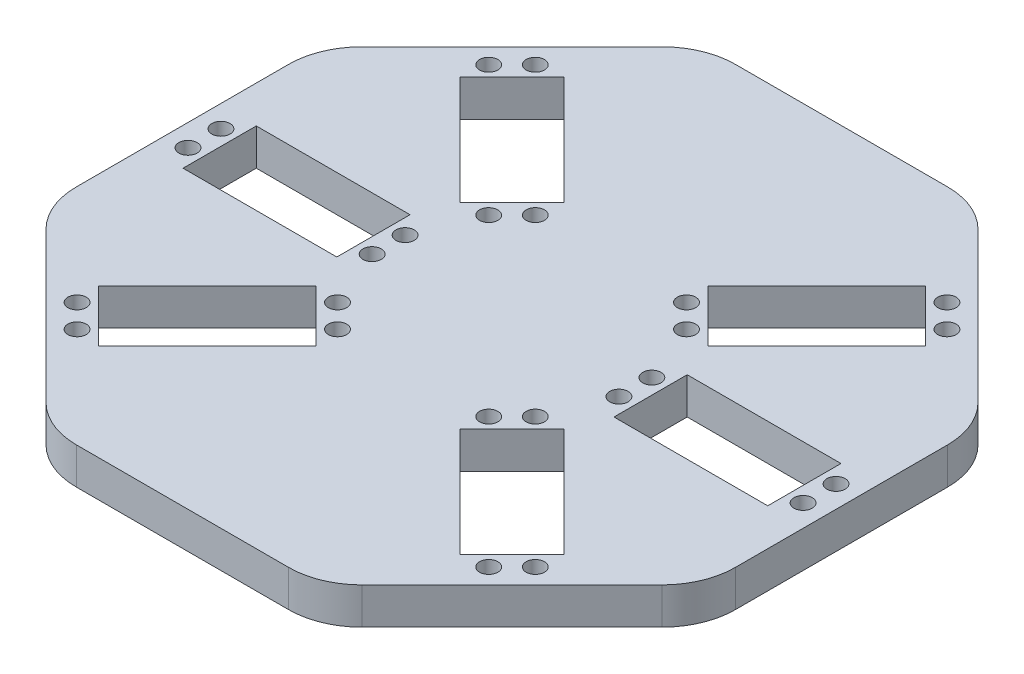
SolidWorks part; units mm, degrees
ref_plane "Front Plane" through (0, 0, 0) normal (0, 0, 1) x (1, 0, 0)
ref_plane "Top Plane" through (0, 0, 0) normal (0, 1, 0) x (1, 0, 0)
ref_plane "Right Plane" through (0, 0, 0) normal (1, 0, 0) x (0, 0, -1)
sketch "Sketch1" plane through (0, 0, 0) normal (0, 1, 0) x (1, 0, 0)
  line L0 (20.6475, -27.0115) -> (56.215, -62.579)
  line L1 (-90, -37.2792) -> (-37.2792, -90)
  line L2 (-37.2792, -90) -> (37.2792, -90)
  line L3 (37.2792, -90) -> (90, -37.2792)
  line L4 (90, -37.2792) -> (90, 37.2792)
  line L5 (90, 37.2792) -> (37.2792, 90)
  line L6 (37.2792, 90) -> (-37.2792, 90)
  line L7 (-37.2792, 90) -> (-90, 37.2792)
  line L8 (-90, 37.2792) -> (-90, -37.2792)
  line L9 (20.6475, -27.0115) -> (27.0115, -20.6475)
  line L10 (56.215, -62.579) -> (62.579, -56.215)
  line L11 (27.0115, -20.6475) -> (62.579, -56.215)
  line L12 (63.6396, -63.6396) -> (0, 0) construction
  line L13 (33.8351, -19.6929) -> (19.6929, -33.8351)
  line L14 (33.8351, -19.6929) -> (63.5335, -49.3914)
  line L15 (19.6929, -33.8351) -> (49.3914, -63.5335)
  line L16 (63.5335, -49.3914) -> (49.3914, -63.5335)
  line L17 (10, -37.85) -> (-10, -37.85) [skipped]
  line L18 (10, -37.85) -> (10, -79.85) [skipped]
  line L19 (10, -79.85) -> (-10, -79.85) [skipped]
  line L20 (-10, -37.85) -> (-10, -79.85) [skipped]
  line L21 (-19.6929, -33.8351) -> (-33.8351, -19.6929)
  line L22 (-19.6929, -33.8351) -> (-49.3914, -63.5335)
  line L23 (-49.3914, -63.5335) -> (-63.5335, -49.3914)
  line L24 (-33.8351, -19.6929) -> (-63.5335, -49.3914)
  line L25 (-37.85, -10) -> (-37.85, 10)
  line L26 (-37.85, -10) -> (-79.85, -10)
  line L27 (-79.85, -10) -> (-79.85, 10)
  line L28 (-37.85, 10) -> (-79.85, 10)
  line L29 (-33.8351, 19.6929) -> (-19.6929, 33.8351)
  line L30 (-33.8351, 19.6929) -> (-63.5335, 49.3914)
  line L31 (-63.5335, 49.3914) -> (-49.3914, 63.5335)
  line L32 (-19.6929, 33.8351) -> (-49.3914, 63.5335)
  line L33 (-10, 37.85) -> (10, 37.85) [skipped]
  line L34 (-10, 37.85) -> (-10, 79.85) [skipped]
  line L35 (-10, 79.85) -> (10, 79.85) [skipped]
  line L36 (10, 37.85) -> (10, 79.85) [skipped]
  line L37 (19.6929, 33.8351) -> (33.8351, 19.6929)
  line L38 (19.6929, 33.8351) -> (49.3914, 63.5335)
  line L39 (49.3914, 63.5335) -> (63.5335, 49.3914)
  line L40 (33.8351, 19.6929) -> (63.5335, 49.3914)
  line L41 (37.85, 10) -> (37.85, -10)
  line L42 (37.85, 10) -> (79.85, 10)
  line L43 (79.85, 10) -> (79.85, -10)
  line L44 (37.85, -10) -> (79.85, -10)
  circle A0 centre (0, 0) radius 90 construction
  circle A5 centre (56.215, -62.579) radius 2.5
  circle A6 centre (62.579, -56.215) radius 2.5
  circle A7 centre (27.0115, -20.6475) radius 2.5
  circle A8 centre (20.6475, -27.0115) radius 2.5
  circle A9 centre (-4.5, -33.7) radius 2.5 [skipped]
  circle A10 centre (4.5, -33.7) radius 2.5 [skipped]
  circle A11 centre (4.5, -84) radius 2.5 [skipped]
  circle A12 centre (-4.5, -84) radius 2.5 [skipped]
  circle A13 centre (0, 0) radius 90 construction
  circle A14 centre (-27.0115, -20.6475) radius 2.5
  circle A15 centre (-20.6475, -27.0115) radius 2.5
  circle A16 centre (-56.215, -62.579) radius 2.5
  circle A17 centre (-62.579, -56.215) radius 2.5
  circle A18 centre (0, 0) radius 90 construction
  circle A19 centre (-33.7, 4.5) radius 2.5
  circle A20 centre (-33.7, -4.5) radius 2.5
  circle A21 centre (-84, -4.5) radius 2.5
  circle A22 centre (-84, 4.5) radius 2.5
  circle A23 centre (0, 0) radius 90 construction
  circle A24 centre (-20.6475, 27.0115) radius 2.5
  circle A25 centre (-27.0115, 20.6475) radius 2.5
  circle A26 centre (-62.579, 56.215) radius 2.5
  circle A27 centre (-56.215, 62.579) radius 2.5
  circle A28 centre (0, 0) radius 90 construction
  circle A29 centre (4.5, 33.7) radius 2.5 [skipped]
  circle A30 centre (-4.5, 33.7) radius 2.5 [skipped]
  circle A31 centre (-4.5, 84) radius 2.5 [skipped]
  circle A32 centre (4.5, 84) radius 2.5 [skipped]
  circle A33 centre (0, 0) radius 90 construction
  circle A34 centre (27.0115, 20.6475) radius 2.5
  circle A35 centre (20.6475, 27.0115) radius 2.5
  circle A36 centre (56.215, 62.579) radius 2.5
  circle A37 centre (62.579, 56.215) radius 2.5
  circle A38 centre (0, 0) radius 90 construction
  circle A39 centre (33.7, -4.5) radius 2.5
  circle A40 centre (33.7, 4.5) radius 2.5
  circle A41 centre (84, 4.5) radius 2.5
  circle A42 centre (84, -4.5) radius 2.5
  circle A43 centre (0, 0) radius 90 construction
  point P15 (63.6396, -63.6396)
  point P16 (59.397, -59.397)
  point P17 (56.4625, -56.4625)
  point P121 (0, 0)
  dimension "D4" = 5
  dimension "D5" = 5
  dimension "D6" = 5
  dimension "D7" = 5
  dimension "D1" = 90
  dimension "D2" = 9
  dimension "D3" = 50.3
  dimension "D8" = 6
  dimension "D9" = 42
  dimension "D10" = 20
  dimension "D11" = 4.15
  dimension "D12" = 8
extrude "Boss-Extrude1" add sketch "Sketch1" along normal blind 10 contours L11 A7 L9 | L9 A7 L11 | L9 A8 L0 | L0 A8 L9 | L11 A6 L10 | L10 A6 L11 | L10 A5 L0 | L0 A5 L10 | L16 L14 L13 L11 | L16 L11 L13 L0 | L16 L0 L13 L15 | L37 L40 L39 L38 | L41 L44 L43 L42 | L29 L32 L31 L30 | L25 L28 L27 L26 | L21 L24 L23 L22 | A22 | A21 | A19 | A20 | A26 | A27 | A24 | A25 | A35 | A34 | A40 | A39 | A41 | A42 | A17 | A16 | A14 | A36 | A37 | L8 L1 L2 L3 L4 L5 L6 L7 | A15 region at (22.148, 0, 27.0115) region at (20.1473, 0, 27.0115) region at (41.6132, 0, 41.6132) region at (36.4867, 0, 46.7398) region at (27.0115, 0, 20.1473) region at (27.0115, 0, 22.148) region at (46.7398, 0, 36.4867) region at (56.215, 0, 61.0784) region at (56.215, 0, 63.0791) region at (63.0791, 0, 56.215) region at (61.0784, 0, 56.215) region at (-41.6132, 0, 41.6132) region at (-58.85, 0, 0) region at (-41.6132, 0, -41.6132) region at (41.6132, 0, -41.6132) region at (58.85, 0, 0) region at (-27.0115, 0, 20.6475) region at (-56.215, 0, 62.579) region at (-62.579, 0, 56.215) region at (-33.7, 0, -4.5) region at (-33.7, 0, 4.5) region at (-84, 0, 4.5) region at (-84, 0, -4.5) region at (-20.6475, 0, -27.0115) region at (-27.0115, 0, -20.6475) region at (-62.579, 0, -56.215) region at (-56.215, 0, -62.579) region at (27.0115, 0, -20.6475) region at (20.6475, 0, -27.0115) region at (56.215, 0, -62.579) region at (62.579, 0, -56.215) region at (33.7, 0, 4.5) region at (33.7, 0, -4.5) region at (84, 0, -4.5) region at (84, 0, 4.5)
fillet "Fillet1" radius 20 8 edges at (-90, 5, -37.2792) (-37.2792, 5, -90) (37.2792, 5, -90) (90, 5, -37.2792) (90, 5, 37.2792) (37.2792, 5, 90) (-37.2792, 5, 90) (-90, 5, 37.2792)
